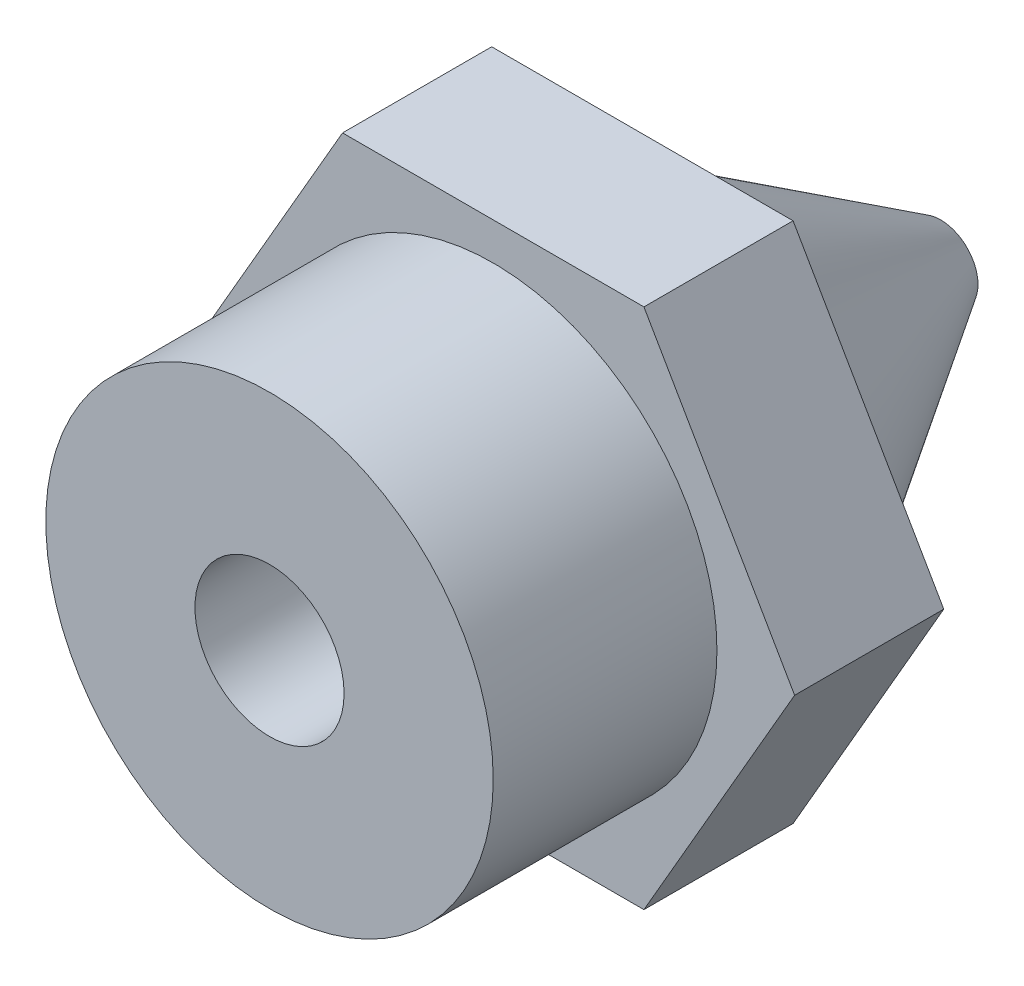
SolidWorks part; units mm, degrees
material "Laiton"
ref_plane "Plan de face" through (0, 0, 0) normal (0, 0, 1) x (1, 0, 0)
ref_plane "Plan de dessus" through (0, 0, 0) normal (0, 1, 0) x (1, 0, 0)
ref_plane "Plan de droite" through (0, 0, 0) normal (1, 0, 0) x (0, 0, -1)
sketch "Esquisse1" plane through (0, 0, 0) normal (0, 0, 1) x (1, 0, 0)
  line L1 (4.0415, 0) -> (2.0207, 3.5)
  line L2 (2.0207, 3.5) -> (-2.0207, 3.5)
  line L3 (-2.0207, 3.5) -> (-4.0415, 0)
  line L4 (-4.0415, 0) -> (-2.0207, -3.5)
  line L5 (-2.0207, -3.5) -> (2.0207, -3.5)
  line L6 (2.0207, -3.5) -> (4.0415, 0)
  circle A0 centre (0, 0) radius 3.5 construction
  dimension "D1" = 7
extrude "Boss.-Extru.1" add sketch "Esquisse1" along normal blind 9 contours L3 L4 L5 L6 L1 L2
sketch "Esquisse2" plane through (0, 0, 9) normal (0, 0, 1) x (1, 0, 0)
  line L1 (-9.4849, 6.2226) -> (10.1391, 6.2226)
  line L2 (-9.4849, 6.2226) -> (-9.4849, -9.3115)
  line L3 (-9.4849, -9.3115) -> (10.1391, -9.3115)
  line L4 (10.1391, 6.2226) -> (10.1391, -9.3115)
  circle A0 centre (0, 0) radius 3
  dimension "D1" = 6
extrude "Enlèv. mat.-Extru.1" cut sketch "Esquisse2" against normal blind 3
cosmetic thread "Représentation de filetage1" parameters "D1"=3, "D2"=4.891
sketch "Esquisse3" plane through (0, 0, 0) normal (0, 0, -1) x (-1, 0, 0)
  line L1 (5.6434, -6.9413) -> (-5.6238, -6.9413)
  line L2 (5.6434, -6.9413) -> (5.6434, 7.0198)
  line L3 (5.6434, 7.0198) -> (-5.6238, 7.0198)
  line L4 (-5.6238, -6.9413) -> (-5.6238, 7.0198)
  circle A0 centre (0, 0) radius 3
  dimension "D1" = 6
extrude "Enlèv. mat.-Extru.2" cut sketch "Esquisse3" against normal blind 4
chamfer "Chanfrein1" distance 4 angle 32 1 edges at (-3, 0, 0) first distance on face at (-3, 0, 4)
sketch "Esquisse4" plane through (0, 0, 0) normal (0, 1, 0) x (1, 0, 0)
  line L0 (0, -10.3816) -> (0, 2.1166) construction
  line L1 (0, -9) -> (1, -9)
  line L2 (-3, -9) -> (3, -9) construction
  line L3 (0, 0) -> (0.15, 0)
  line L4 (0.15, 0) -> (1, -6.9227)
  line L5 (0, -9) -> (0, 0)
  line L9 (1, -6.9227) -> (1, -9)
  dimension "D1" = 1
  dimension "D2" = 0.15
  dimension "D3" = 7
  dimension "D4" = 2.0773
revolve "Enlèvement de matière-Révolution1" cut sketch "Esquisse4" angle 360 about L0
